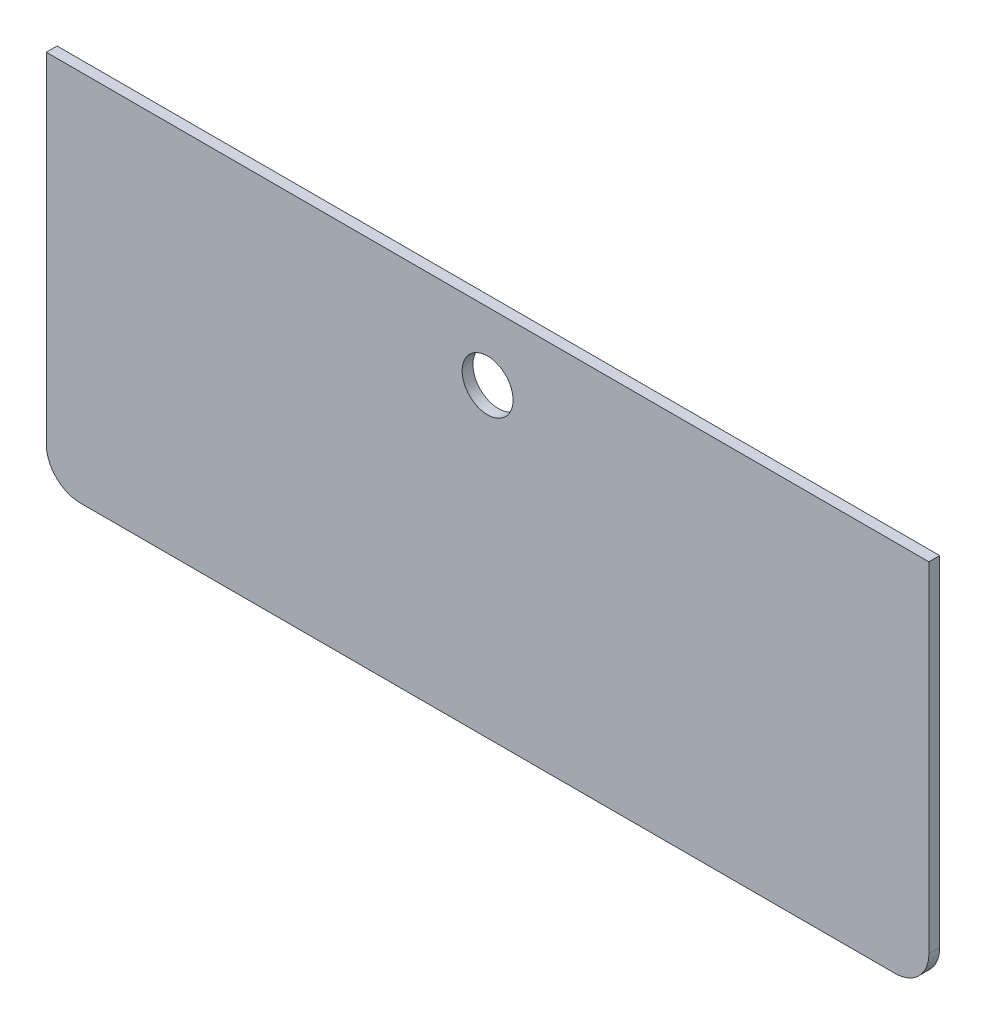
SolidWorks part; units mm, degrees
ref_plane "Front Plane" through (0, 0, 0) normal (0, 0, 1) x (1, 0, 0)
ref_plane "Top Plane" through (0, 0, 0) normal (0, 1, 0) x (1, 0, 0)
ref_plane "Right Plane" through (0, 0, 0) normal (1, 0, 0) x (0, 0, -1)
sketch "Sketch1" plane through (0, 0, 0) normal (0, 0, 1) x (1, 0, 0)
  line L0 (-156.7654, 27.1868) -> (-156.7654, -82.8132)
  line L1 (-156.7654, -82.8132) -> (103.2346, -82.8132)
  line L2 (103.2346, -82.8132) -> (103.2346, 27.1868)
  line L3 (103.2346, 27.1868) -> (-156.7654, 27.1868)
  line L4 (-26.7654, 27.1868) -> (-26.7654, 7.1868) construction
  circle A0 centre (-26.7654, 7.1868) radius 7.5
  dimension "D4" = 15
  dimension "D1" = 110
  dimension "D2" = 260
  dimension "D3" = 20
extrude "Boss-Extrude1" add sketch "Sketch1" along normal blind 3.175
fillet "Fillet1" radius 10 2 edges at (-156.7654, -82.8132, 1.5875) (103.2346, -82.8132, 1.5875)
equation "\"L\"= 500"
equation "\"W\"= 260"
equation "\"H\"= 110"
equation "\"Compartment Width\"= 100"
equation "\"T\"= 4.7625 * 2 / 3"
equation "\"Inside Fillet Radius\"= 10"
equation "\"D1@Boss-Extrude1\"=\"T\""
equation "\"D1@Fillet1\"=\"Inside Fillet Radius\""
equation "\"Hole\"=15"
equation "\"D4@Sketch1\"=\"Hole\""
equation "\"D2@Sketch1\"=\"W\""
equation "\"D1@Sketch1\"=\"H\""
